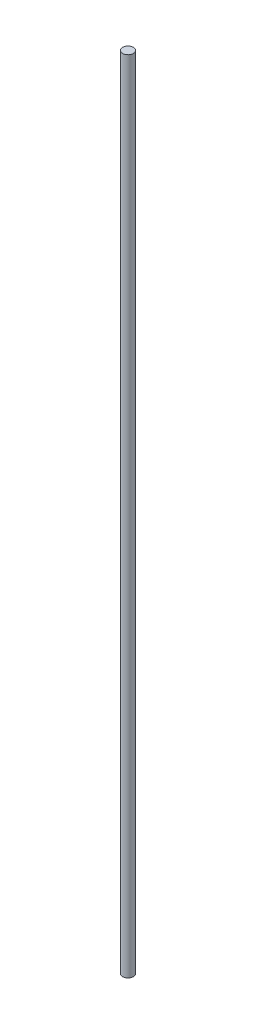
SolidWorks part; units mm, degrees
material "AISI 1020"
ref_plane "Front Plane" through (0, 0, 0) normal (0, 0, 1) x (1, 0, 0)
ref_plane "Top Plane" through (0, 0, 0) normal (0, 1, 0) x (1, 0, 0)
ref_plane "Right Plane" through (0, 0, 0) normal (1, 0, 0) x (0, 0, -1)
sketch "Sketch1" plane through (0, 0, 0) normal (0, 1, 0) x (1, 0, 0)
  circle A0 centre (0, 0) radius 1.6193
  dimension "D1" = 3.2385
extrude "Boss-Extrude1" add sketch "Sketch1" along normal blind 241.3
